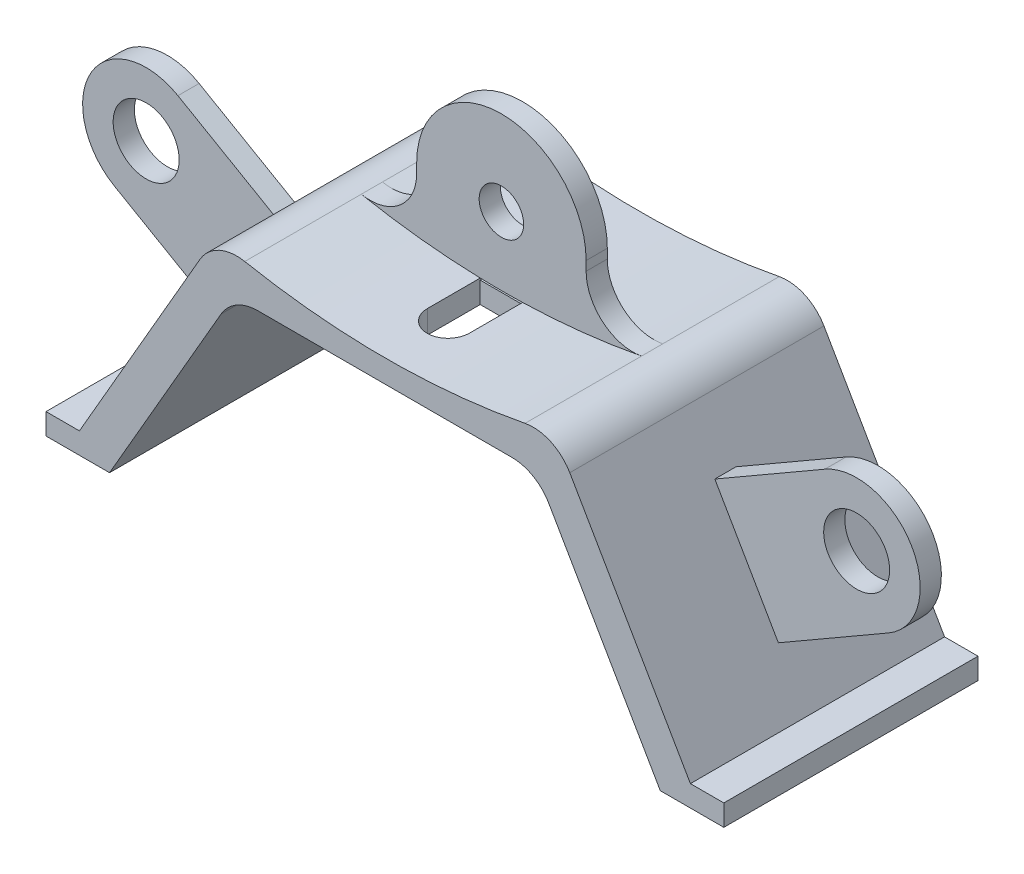
SolidWorks part; units mm, degrees
ref_plane "Plan de face" through (0, 0, 0) normal (0, 0, 1) x (1, 0, 0)
ref_plane "Plan de dessus" through (0, 0, 0) normal (0, 1, 0) x (1, 0, 0)
ref_plane "Plan de droite" through (0, 0, 0) normal (1, 0, 0) x (0, 0, -1)
sketch "Esquisse1" plane through (0, 0, 0) normal (0, 0, 1) x (1, 0, 0)
  line L0 (0, 0) -> (29.2265, 50.6218)
  line L1 (29.2265, 50.6218) -> (100.7735, 50.6218)
  line L2 (100.7735, 50.6218) -> (130, 0)
  line L3 (130, 0) -> (140, 0)
  line L4 (140, 0) -> (105, 60.6218)
  line L5 (105, 60.6218) -> (25, 60.6218)
  line L6 (25, 60.6218) -> (-10, 0)
  line L7 (-10, 0) -> (0, 0)
  point P8 (0, 0)
  dimension "D1" = 10
  dimension "D2" = 120
  dimension "D3" = 70
  dimension "D4" = 80
  dimension "D5" = 10
extrude "Boss.-Extru.1" add sketch "Esquisse1" along normal blind 60
sketch "Esquisse2" plane through (0, 0, 0) normal (0, 0, -1) x (-1, 0, 0)
  line L1 (-29.2265, 50.6218) -> (-100.7735, 50.6218) construction
  line L2 (-105, 60.6218) -> (-25, 60.6218) construction
  line L3 (-105, 60.6218) -> (-25, 60.6218)
  arc A0 (-105, 60.6218) -> (-25, 60.6218) centre (-65, 230.6218) ccw
  dimension "D1" = 180
extrude "Enlèv. mat.-Extru.1" cut sketch "Esquisse2" against normal blind 60
fillet "Congé1" radius 10 2 edges at (25, 60.6218, 30) (105, 60.6218, 30)
sketch "Esquisse3" plane through (0, 0, 0) normal (0, 1, 0) x (1, 0, 0)
  line L0 (31.9176, -60) -> (98.0824, -60) construction
  line L3 (31.9176, -60) -> (98.0824, -60) construction
  line L6 (65, -60) -> (65, 0) construction
  line L7 (98.0824, 0) -> (31.9176, 0) construction
  line L8 (65, -15) -> (65, -45) construction
  line L9 (70, -15) -> (70, -45)
  line L10 (60, -15) -> (60, -45)
  arc A2 (70, -15) -> (60, -15) centre (65, -15) ccw
  arc A3 (60, -45) -> (70, -45) centre (65, -45) ccw
  point P8 (65, -30)
  dimension "D2" = 5
  dimension "D1" = 30
extrude "Enlèv. mat.-Extru.2" cut sketch "Esquisse3" along normal blind 60
fillet "Congé2" radius 10 2 edges at (100.7735, 50.6218, 30) (29.2265, 50.6218, 30)
sketch "Esquisse4" plane through (0, 0, 0) normal (0, -1, 0) x (1, 0, 0)
  line L0 (0, 0) -> (-15, 0)
  line L1 (-15, 0) -> (-15, 60)
  line L2 (-15, 60) -> (0, 60)
  line L3 (-10, 60) -> (0, 60) construction
  line L4 (0, 60) -> (0, 0) construction
  line L5 (65, 68.8408) -> (65, -12.1071) construction
  line L6 (130, 0) -> (145, 0)
  line L7 (145, 0) -> (145, 60)
  line L8 (145, 60) -> (130, 60)
  line L9 (0, 60) -> (0, 0)
  line L10 (130, 60) -> (130, 0)
  dimension "D1" = 15
extrude "Boss.-Extru.2" add sketch "Esquisse4" against normal blind 5
sketch "Esquisse5" plane through (0, 0, 60) normal (0, 0, 1) x (1, 0, 0)
  line L1 (21.363, 54.3224) -> (-7.1132, 5) construction
  line L2 (115.3751, 42.6516) -> (141.3559, 57.6516)
  line L3 (14.6249, 42.6516) -> (-0.3751, 16.6708)
  line L4 (65, 55.9793) -> (65, 86.2928) construction
  line L5 (45, 72.1283) -> (45, 57.1283)
  line L6 (85, 72.1283) -> (85, 57.1283)
  line L7 (7.1249, 29.6612) -> (-28.3126, 50.121) construction
  line L8 (-0.3751, 16.6708) -> (-26.3559, 31.6708)
  line L9 (14.6249, 42.6516) -> (-11.3559, 57.6516)
  line L10 (130.3751, 16.6708) -> (156.3559, 31.6708)
  line L11 (115.3751, 42.6516) -> (130.3751, 16.6708)
  arc A0 (31.9176, 59.1413) -> (98.0824, 59.1413) centre (65, 230.6218) ccw construction
  arc A1 (45, 57.1283) -> (85, 57.1283) centre (65, 230.6218) ccw
  arc A2 (45, 72.1283) -> (85, 72.1283) centre (65, 72.1283) cw
  circle A3 centre (65, 72.1283) radius 5.25
  arc A4 (-26.3559, 31.6708) -> (-11.3559, 57.6516) centre (-18.8559, 44.6612) cw
  circle A5 centre (-18.8559, 44.6612) radius 7.7898
  circle A6 centre (148.8559, 44.6612) radius 7.7898
  arc A7 (156.3559, 31.6708) -> (141.3559, 57.6516) centre (148.8559, 44.6612) ccw
  dimension "D5" = 10.5
  dimension "D1" = 20
  dimension "D2" = 15
  dimension "D3" = 15
  dimension "D4" = 30
extrude "Boss.-Extru.3" add sketch "Esquisse5" against normal blind 5 from offset 27.5 offset against normal yes
sketch "Esquisse6" plane through (0, 50.6218, 0) normal (0, -1, 0) x (1, 0, 0)
  line L4 (70, 32.5) -> (60, 32.5)
  line L5 (60, 32.5) -> (60, 27.5)
  line L6 (60, 27.5) -> (70, 27.5)
  line L7 (70, 27.5) -> (70, 32.5)
  line L8 (70, 32.5) -> (60, 32.5)
  line L9 (60, 32.5) -> (60, 27.5)
  line L10 (60, 27.5) -> (70, 27.5)
  line L11 (70, 27.5) -> (70, 32.5)
  dimension "D1" = 0
extrude "Boss.-Extru.4" add sketch "Esquisse6" against normal blind 5
fillet "Congé3" radius 11 2 edges at (45, 57.1283, 30) (85, 57.1283, 30)
